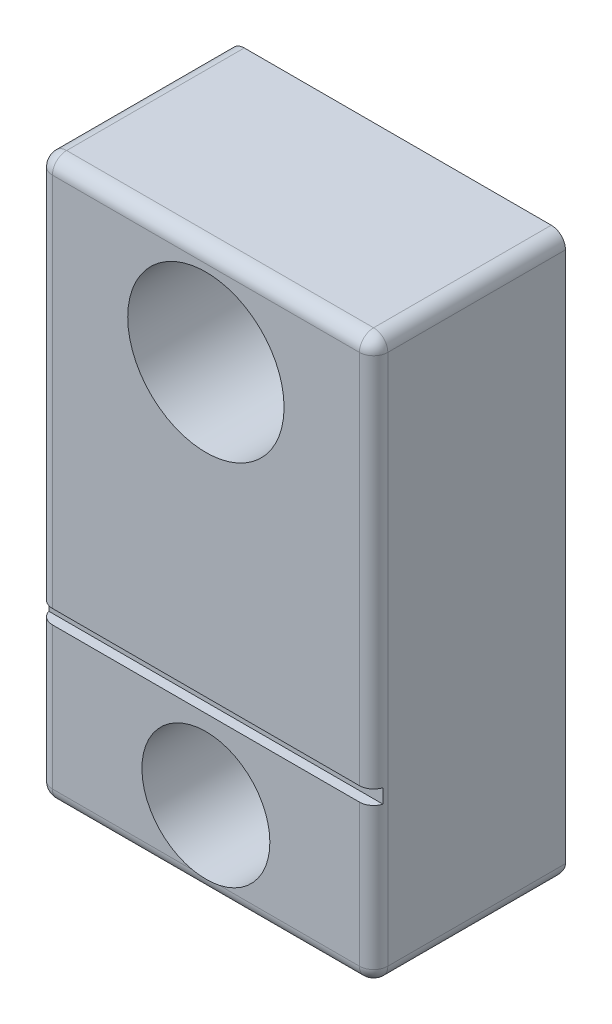
SolidWorks part; units mm, degrees
ref_plane "Front Plane" through (0, 0, 0) normal (0, 0, 1) x (1, 0, 0)
ref_plane "Top Plane" through (0, 0, 0) normal (0, 1, 0) x (1, 0, 0)
ref_plane "Right Plane" through (0, 0, 0) normal (1, 0, 0) x (0, 0, -1)
sketch "Sketch1" plane through (0, 0, 0) normal (0, 0, 1) x (1, 0, 0)
  line L1 (-1.18, 1.97) -> (1.18, 1.97)
  line L2 (-1.18, 1.97) -> (-1.18, -1.97)
  line L3 (-1.18, -1.97) -> (1.18, -1.97)
  line L4 (1.18, 1.97) -> (1.18, -1.97)
  line L5 (-1.18, 1.97) -> (1.18, -1.97) construction
  line L6 (-1.18, -1.97) -> (1.18, 1.97) construction
  point P0 (0, 0)
  dimension "D1" = 3.94
  dimension "D2" = 2.36
extrude "Boss-Extrude1" add sketch "Sketch1" along normal blind 1.35
sketch "Sketch2" plane through (1.18, 0, 0) normal (1, 0, 0) x (0, 0, -1)
  line L0 (-1.35, -0.82) -> (0, -0.82) construction
  line L1 (-1.35, -1.97) -> (-1.35, 1.97) construction
  line L2 (0, -1.97) -> (0, 1.97) construction
  line L3 (-1.35, -1.97) -> (0, -1.97) construction
  line L4 (-1.35, -0.77) -> (-1.35, -0.87)
  line L5 (-1.35, -0.87) -> (-1.28, -0.87)
  line L6 (-1.28, -0.87) -> (-1.28, -0.77)
  line L7 (-1.28, -0.77) -> (-1.35, -0.77)
  point P11 (-1.35, -0.82)
  dimension "D1" = 1.15
  dimension "D2" = 0.1
  dimension "D3" = 0.07
extrude "Cut-Extrude1" cut sketch "Sketch2" against normal through all
fillet "Fillet2" radius 0.1 9 edges at (-1.18, -1.97, 0.675) (0, -1.97, 1.35) (1.18, -1.97, 0.675) (0, -1.97, 0) (-1.18, 1.97, 0.675) (1.18, 1.97, 0.675) (0, 1.97, 1.35) (1.18, 0.6, 1.35) (-1.18, 0.6, 1.35)
sketch "Sketch3" plane through (0, 0, 1.35) normal (0, 0, 1) x (1, 0, 0)
  line L0 (0, 1.97) -> (0, -1.97) construction
  line L3 (-1.08, 1.97) -> (1.08, 1.97) construction
  line L5 (1.08, -1.97) -> (-1.08, -1.97) construction
  circle A0 centre (0, 1.27) radius 0.55
  circle A1 centre (0, -1.43) radius 0.45
  dimension "D3" = 0.9
  dimension "D4" = 1.1
  dimension "D1" = 0.54
  dimension "D2" = 2.7
extrude "Cut-Extrude2" cut sketch "Sketch3" against normal blind 1
